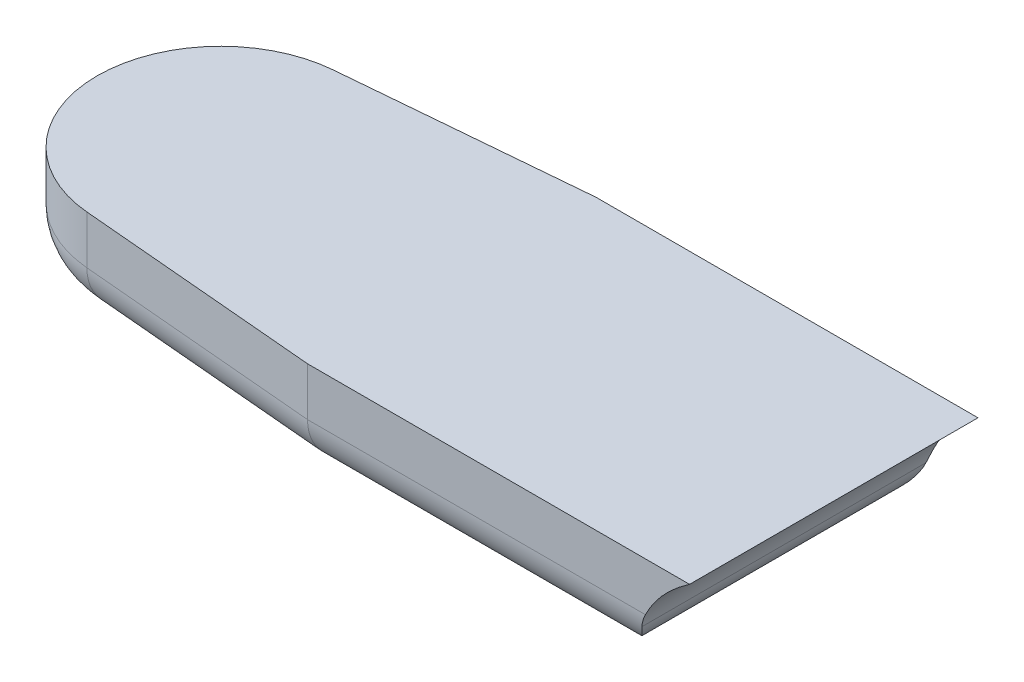
SolidWorks part; units mm, degrees
ref_plane "前视基准面" through (0, 0, 0) normal (0, 0, 1) x (1, 0, 0)
ref_plane "上视基准面" through (0, 0, 0) normal (0, 1, 0) x (1, 0, 0)
ref_plane "右视基准面" through (0, 0, 0) normal (1, 0, 0) x (0, 0, -1)
sketch "草图3" plane through (0, 0, 0) normal (0, 1, 0) x (1, 0, 0)
  line L0 (163.7303, -29.8251) -> (80.5797, -29.8251)
  line L1 (80.5797, -29.8251) -> (30.5797, -25.4506)
  line L2 (30.5797, 25.4506) -> (80.5797, 29.8251)
  line L3 (80.5797, 29.8251) -> (163.7303, 29.8251)
  line L4 (163.7303, 29.8251) -> (163.7303, -29.8251)
  line L5 (30.5797, -25.4506) -> (30.5797, 25.4506) construction
  line L7 (80.5797, 29.8251) -> (0, 25.6021) construction
  line L8 (0, -25.6021) -> (80.5797, -29.8251) construction
  arc A1 (30.5797, -25.4506) -> (30.5797, 25.4506) centre (32.8064, 0) cw
  dimension "D1" = 50
  dimension "D2" = 50
  dimension "D3" = 2
  dimension "D4" = 2
extrude "凸台-拉伸1" add sketch "草图3" against normal blind 20 contours L2 L3 L4 L0 L1 A1
sketch "草图4" plane through (0, 0, 0) normal (0, 0, 1) x (1, 0, 0)
  line L0 (163.7303, 0) -> (159.5807, 0)
  line L1 (163.7303, 0) -> (80.5797, 0) construction
  line L2 (163.7303, -20) -> (80.5797, -20) construction
  line L3 (148.3027, -20) -> (203.2217, -20)
  line L4 (203.2217, -20) -> (203.2217, 0)
  line L5 (203.2217, 0) -> (163.7303, 0)
  spline S0 degree 2 poles (159.5807, 0) (148.1221, -7.8244) (148.3027, -20) knots 0 0 0 1 1 1
extrude "切除-拉伸1" cut sketch "草图4" against normal through all both and the other way through all
fillet "圆角1" radius 10 6 edges at (148.3027, -20, 0) (114.4412, -20, -29.8251) (114.4412, -20, 29.8251) (55.5797, -20, 27.6379) (55.5797, -20, -27.6379) (7.2585, -20, 0)
